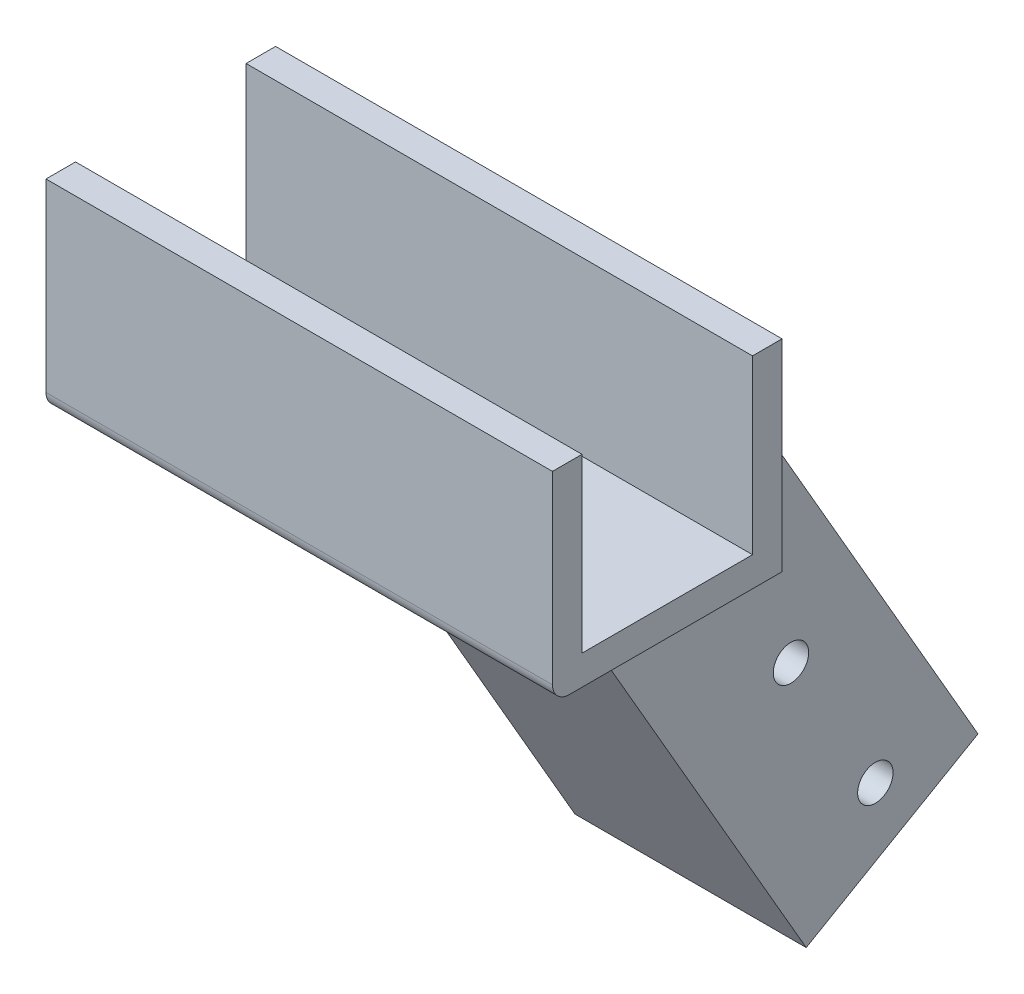
SolidWorks part; units mm, degrees
material "Custom Plastic"
ref_plane "Front Plane" through (0, 0, 0) normal (0, 0, 1) x (1, 0, 0)
ref_plane "Top Plane" through (0, 0, 0) normal (0, 1, 0) x (1, 0, 0)
ref_plane "Right Plane" through (0, 0, 0) normal (1, 0, 0) x (0, 0, -1)
sketch "Sketch1" plane through (0, 0, 0) normal (1, 0, 0) x (0, 0, -1)
  line L1 (-13.6, -11.95) -> (13.6, -11.95)
  line L2 (-13.6, -11.95) -> (-13.6, 11.95)
  line L3 (-13.6, 11.95) -> (13.6, 11.95)
  line L4 (13.6, -11.95) -> (13.6, 11.95)
  line L5 (-13.6, -11.95) -> (13.6, 11.95) construction
  line L6 (-13.6, 11.95) -> (13.6, -11.95) construction
  point P0 (0, 0)
  dimension "D1" = 27.2
  dimension "D2" = 23.9
extrude "Boss-Extrude1" add sketch "Sketch1" along normal mid plane 60
shell "Shell1" thickness 3.5 removed face at (30, 0, 0) removed face at (-30, 0, 0) removed face at (0, 11.95, 0)
sketch "Sketch2" plane through (0, 0, 0) normal (1, 0, 0) x (0, 0, -1)
  line L0 (0.2632, -11.95) -> (32.7632, -68.2417)
  line L1 (13.6, 11.95) -> (10.1, 11.95) construction
  line L2 (32.7632, -68.2417) -> (53.1148, -56.4917)
  line L3 (53.1148, -56.4917) -> (13.6, 11.95)
  line L4 (13.6, -11.95) -> (13.6, 11.95) construction
  line L5 (-13.6, -11.95) -> (13.6, -11.95) construction
  line L7 (0.2632, -11.95) -> (13.6, -11.95)
  line L8 (13.6, -11.95) -> (13.6, 11.95)
  point P2 (13.6, 11.95)
  point P4 (13.6, 7.8111)
  dimension "D1" = 150
  dimension "D2" = 23.5
  dimension "D4" = 65
extrude "Boss-Extrude2" add sketch "Sketch2" along normal mid plane 27.4
shell "Shell3" thickness 3.5 removed face at (0, -62.3667, -42.939) removed face at (0, -22.2708, -33.3574)
fillet "Fillet2" radius 2 1 edges at (0, -11.95, 13.6)
sketch "Sketch3" plane through (13.7, 0, 0) normal (1, 0, 0) x (0, 0, -1)
  line L0 (44.4546, -61.4917) -> (13.6, -8.05) construction
  line L1 (32.7632, -68.2417) -> (53.1148, -56.4917) construction
  line L3 (53.1148, -56.4917) -> (13.6, 11.95) construction
  line L4 (13.6, 11.95) -> (13.6, -11.95) construction
  circle A0 centre (40.9546, -55.4295) radius 2.1
  circle A1 centre (30.9546, -38.109) radius 2.1
  circle A2 centre (20.9546, -20.7885) radius 2.1
  point P4 (13.6, -7.8701)
  point P11 (0, 0)
  dimension "D2" = 4.2
  dimension "D3" = 7
  dimension "D5" = 20
  dimension "D1" = 10
  dimension "D4" = 3
extrude "Cut-Extrude1" cut sketch "Sketch3" against normal through all
fillet "Fillet3" radius 10 1 edges at (0, -11.95, -0.2632)
